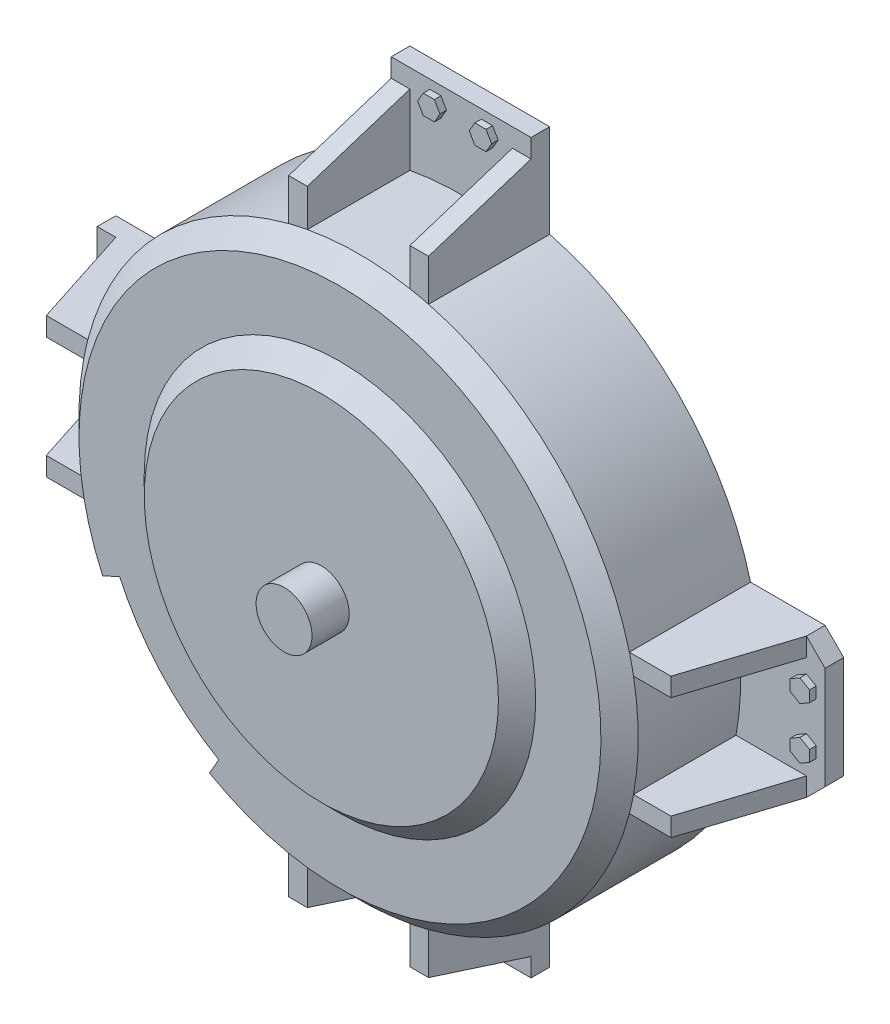
SolidWorks part; units mm, degrees
ref_plane "Front Plane" through (0, 0, 0) normal (0, 0, 1) x (1, 0, 0)
ref_plane "Top Plane" through (0, 0, 0) normal (0, 1, 0) x (1, 0, 0)
ref_plane "Right Plane" through (0, 0, 0) normal (1, 0, 0) x (0, 0, -1)
sketch "Sketch2" plane through (0, 0, 0) normal (0, 0, 1) x (1, 0, 0)
  circle A0 centre (0, 0) radius 150
  dimension "D1" = 300
extrude "Boss-Extrude1" add sketch "Sketch2" along normal blind 75
chamfer "Chamfer1" distance 10 angle 45 1 edges at (150, 0, 75)
sketch "Sketch4" plane through (0, 0, 0) normal (0, 0, -1) x (-1, 0, 0)
  line L1 (-195.2369, 37.5) -> (-145.2369, 37.5)
  line L2 (-195.2369, 37.5) -> (-195.2369, -37.5)
  line L3 (-195.2369, -37.5) -> (-145.2369, -37.5)
  circle A0 centre (0, 0) radius 150 construction
  circle A1 centre (0, 0) radius 150
  point P0 (-150, 0)
  circle M5 centre (0, 0) radius 150
  dimension "D1" = 75
  dimension "D2" = 50
extrude "Boss-Extrude2" add sketch "Sketch4" against normal blind 10 contours L2 L3 L1 M5 region at (171.8083, 0, 0)
chamfer "Chamfer2" distance 10 angle 45 2 edges at (195.2369, -37.5, 5) (195.2369, 37.5, 5)
sketch "Sketch6" plane through (0, 37.5, 0) normal (0, 1, 0) x (1, 0, 0)
  line L0 (120.2369, -10) -> (120.2369, -65)
  line L1 (185.2369, -10) -> (145.2369, -10) construction
  line L2 (150, -65) -> (-150, -65) construction
  line L3 (120.2369, -65) -> (167.5569, -65)
  line L4 (167.5569, -65) -> (185.2369, -10)
  line L5 (185.2369, -10) -> (120.2369, -10)
  line L6 (185.2369, -10) -> (185.2369, 0) construction
  dimension "D1" = 17.68
  dimension "D2" = 65
extrude "Boss-Extrude3" add sketch "Sketch6" against normal blind 10
sketch "Sketch7" plane through (0, 0, 10) normal (0, 0, 1) x (1, 0, 0)
  line L0 (185.2369, 37.5) -> (185.2369, -61.0887) construction
  line L2 (185.2369, 7.846) -> (190.433, 10.846)
  line L3 (190.433, 10.846) -> (190.433, 16.846)
  line L4 (190.433, 16.846) -> (185.2369, 19.846)
  line L5 (185.2369, 19.846) -> (180.0407, 16.846)
  line L6 (180.0407, 16.846) -> (180.0407, 10.846)
  line L7 (180.0407, 10.846) -> (185.2369, 7.846)
  circle A0 centre (185.2369, 13.846) radius 5.1962 construction
  dimension "D1" = 6
extrude "Boss-Extrude4" add sketch "Sketch7" along normal blind 3.5
mirror "Mirror1" about plane through (0, 0, 0) normal (0, 1, 0) of "Boss-Extrude4", "Boss-Extrude3"
pattern_circular "CirPattern1" count 4 every 90 about axis through (0, 0, 0) along (0, 0, 1) of "Mirror1", "Boss-Extrude2", "Boss-Extrude3", "Boss-Extrude4"
sketch "Sketch9" plane through (0, 0, 75) normal (0, 0, 1) x (1, 0, 0)
  line L3 (-118.1912, -54.1371) -> (-136.3745, -62.4659)
  line L4 (-65, -112.5833) -> (-75, -129.9038)
  arc A0 (-118.1912, -54.1371) -> (-65, -112.5833) centre (0, 0) ccw
  arc A1 (-145.2369, -37.5) -> (-37.5, -145.2369) centre (0, 0) ccw construction
  arc A2 (-136.3745, -62.4659) -> (-75, -129.9038) centre (0, 0) ccw
  dimension "D3" = 260
extrude "Cut-Extrude1" cut sketch "Sketch9" against normal blind 60
sketch "Sketch10" plane through (0, 0, 75) normal (0, 0, 1) x (1, 0, 0)
  circle A0 centre (0, 0) radius 110
  dimension "D1" = 220
extrude "Boss-Extrude5" add sketch "Sketch10" along normal blind 10
chamfer "Chamfer3" distance 15 angle 45 1 edges at (110, 0, 85)
sketch "Sketch11" plane through (0, 0, 85) normal (0, 0, 1) x (1, 0, 0)
  circle A0 centre (0, 0) radius 15
  dimension "D1" = 30
extrude "Boss-Extrude6" add sketch "Sketch11" along normal blind 20
